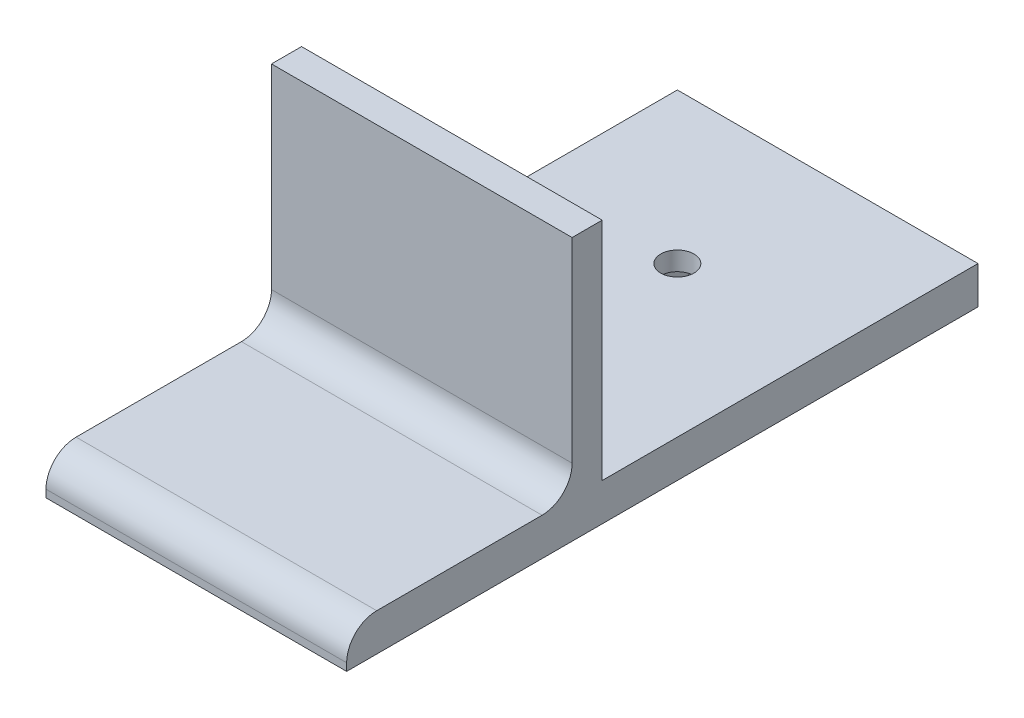
SolidWorks part; units mm, degrees
ref_plane "Front Plane" through (0, 0, 0) normal (0, 0, 1) x (1, 0, 0)
ref_plane "Top Plane" through (0, 0, 0) normal (0, 1, 0) x (1, 0, 0)
ref_plane "Right Plane" through (0, 0, 0) normal (1, 0, 0) x (0, 0, -1)
sketch "Sketch1" plane through (0, 0, 0) normal (1, 0, 0) x (0, 0, -1)
  line L0 (0, 0) -> (106.68, 0)
  line L1 (106.68, 0) -> (106.68, 6.35)
  line L6 (0, 6.35) -> (0, 0)
  line L7 (43.18, 44.45) -> (43.18, 6.35)
  line L8 (43.18, 6.35) -> (106.68, 6.35)
  line L10 (0, 6.35) -> (38.1, 6.35)
  line L11 (38.1, 6.35) -> (38.1, 44.45)
  line L12 (38.1, 44.45) -> (43.18, 44.45)
  point P3 (0, 0)
  point P5 (106.68, 6.35)
  dimension "D1" = 5.08
  dimension "D2" = 63.5
  dimension "D3" = 6.35
  dimension "D4" = 38.1
  dimension "D6" = 38.1
extrude "Boss-Extrude1" add sketch "Sketch1" along normal blind 50.8
sketch "Sketch2" plane through (0, 0, 0) normal (-1, 0, 0) x (0, 0, 1)
  line L0 (-43.18, 6.35) -> (-43.18, 44.45) construction
  line L1 (-63.5, 6.35) -> (-43.18, 6.35)
  line L2 (-63.5, 6.35) -> (-63.5, 44.45)
  line L3 (-63.5, 44.45) -> (-43.18, 44.45)
  line L4 (-43.18, 6.35) -> (-43.18, 44.45)
extrude "Boss-Extrude2" [suppressed] add sketch "Sketch2" against normal blind 2.54
sketch "Sketch4" plane through (50.8, 0, 0) normal (1, 0, 0) x (0, 0, -1)
  line L0 (63.5, 44.45) -> (63.5, 6.35) construction
  line L1 (63.5, 20.32) -> (59.69, 20.32)
  line L2 (63.5, 20.32) -> (63.5, 25.4)
  line L3 (63.5, 25.4) -> (59.69, 25.4)
  line L4 (59.69, 20.32) -> (59.69, 25.4)
  line L5 (106.68, 6.35) -> (43.18, 6.35) construction
  dimension "D1" = 3.81
  dimension "D2" = 13.97
  dimension "D3" = 5.08
extrude "Boss-Extrude5" [suppressed] add sketch "Sketch4" against normal blind 50.8
hole_wizard "#10 Clearance Hole1" positions "Sketch6" profile "Sketch7" hole size "#10" standard "ANSI Inch" end condition through all
sketch "Sketch6" plane through (0, 6.35, 0) normal (0, 1, 0) x (1, 0, 0)
  line L0 (50.8, 43.18) -> (0, 43.18) construction
  line L1 (25.4, 106.68) -> (25.4, 81.28) construction
  line L2 (50.8, 106.68) -> (0, 106.68) construction
  point P0 (25.4, 81.28)
  dimension "D1" = 38.1
sketch "Sketch7" plane through (25.4, 6.35, -81.28) normal (1, 0, 0) x (0, 0, 1)
  line L0 (0, 0) -> (0, 6.35)
  line L1 (0, 6.35) -> (2.8067, 6.35)
  line L2 (2.8067, 6.35) -> (2.8067, 0)
  line L5 (2.8067, 0) -> (0, 0)
  line L11 (0, -6.35) -> (0, 107.95) construction
  dimension "Thru Hole Dia." = 5.6134
  dimension "Thru Hole Depth" = 6.35
sketch "Sketch8" plane through (0, 0, 0) normal (0, -1, 0) x (1, 0, 0)
  line L1 (28.0792, -85.8183) -> (30.6699, -81.2289)
  line L2 (30.6699, -81.2289) -> (27.9907, -76.6906)
  line L3 (27.9907, -76.6906) -> (22.7208, -76.7417)
  line L4 (22.7208, -76.7417) -> (20.1301, -81.3311)
  line L5 (20.1301, -81.3311) -> (22.8093, -85.8694)
  line L6 (22.8093, -85.8694) -> (28.0792, -85.8183)
  circle A0 centre (25.4, -81.28) radius 4.5641 construction
  dimension "D1" = 9.1281
extrude "Cut-Extrude1" cut sketch "Sketch8" against normal blind 3.175
fillet "Fillet1" radius 5.08 2 edges at (25.4, 6.35, 0) (25.4, 6.35, -38.1)
